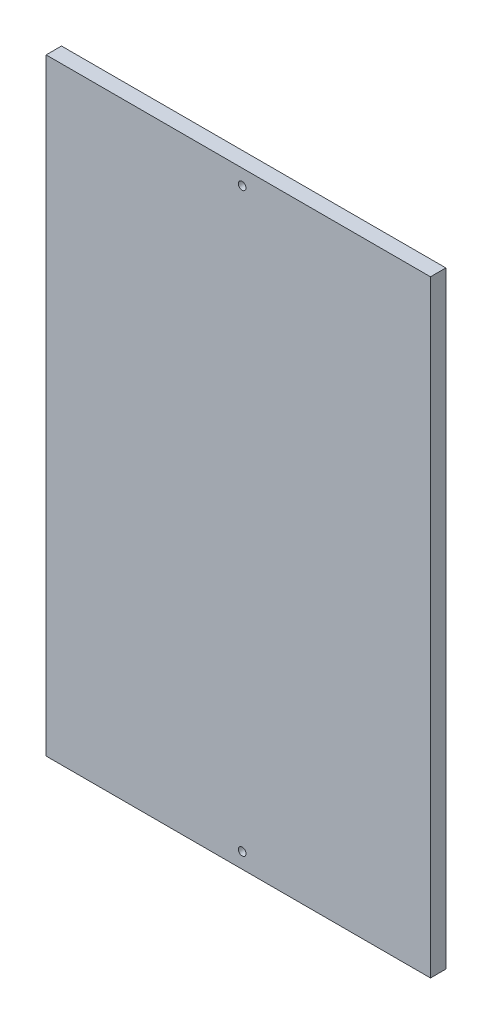
SolidWorks part; units mm, degrees
ref_plane "Plan de face" through (0, 0, 0) normal (0, 0, 1) x (1, 0, 0)
ref_plane "Plan de dessus" through (0, 0, 0) normal (0, 1, 0) x (1, 0, 0)
ref_plane "Plan de droite" through (0, 0, 0) normal (1, 0, 0) x (0, 0, -1)
sketch "Esquisse1" plane through (0, 0, 0) normal (0, 0, 1) x (1, 0, 0)
  line L1 (212.3378, 73.6472) -> (-37.6622, 73.6472)
  line L2 (212.3378, 73.6472) -> (212.3378, -321.3528)
  line L3 (212.3378, -321.3528) -> (-37.6622, -321.3528)
  line L4 (-37.6622, 73.6472) -> (-37.6622, -321.3528)
  circle A0 centre (89.8378, 63.6472) radius 2.5
  circle A1 centre (89.8378, -311.3528) radius 2.5
  dimension "D3" = 5
  dimension "D6" = 5
  dimension "D7" = 10
  dimension "D8" = 127.5
  dimension "D1" = 250
  dimension "D2" = 395
  dimension "D4" = 10
  dimension "D5" = 375
extrude "Boss.-Extru.1" add sketch "Esquisse1" along normal blind 10
